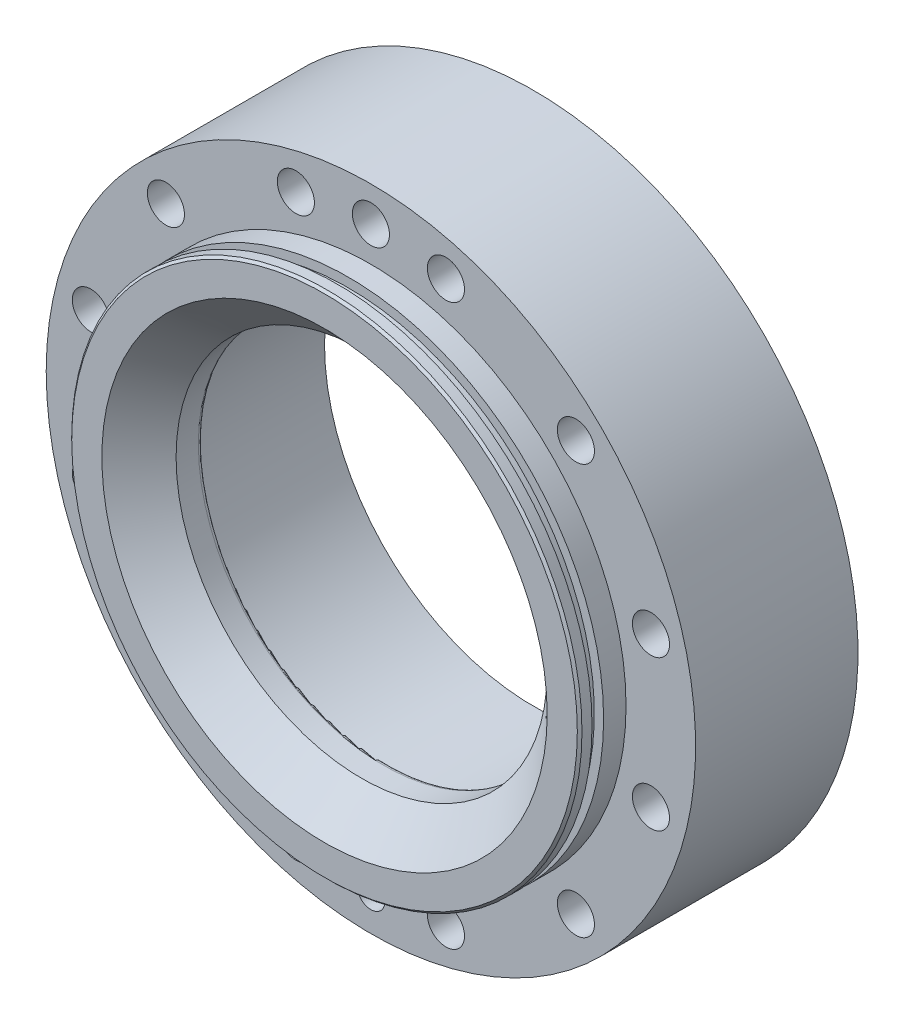
SolidWorks part; units mm, degrees
ref_plane "Front Plane" through (0, 0, 0) normal (0, 0, 1) x (1, 0, 0)
ref_plane "Top Plane" through (0, 0, 0) normal (0, 1, 0) x (1, 0, 0)
ref_plane "Right Plane" through (0, 0, 0) normal (1, 0, 0) x (0, 0, -1)
sketch "Sketch1" plane through (0, 0, 0) normal (0, 1, 0) x (1, 0, 0)
  line L0 (-55, -19.7958) -> (-55, -9.7958)
  line L2 (-55, -9.7958) -> (-70, -9.7958)
  line L3 (-55, -19.7958) -> (-40, -19.7958)
  line L4 (-40, -19.7958) -> (-40, -6)
  line L5 (-40, -6) -> (-45, -6)
  line L6 (-45, -6) -> (-45, 25.2042)
  line L7 (-45, 25.2042) -> (-70, 25.2042)
  line L8 (-70, 25.2042) -> (-70, -9.7958)
  line L12 (0, 52.7074) -> (0, -119.6493) construction
  point P2 (0, 0)
  point P3 (0, 0)
  dimension "D1" = 15
  dimension "D2" = 31.2042
revolve "Revolve1" add sketch "Sketch1" angle 360 about L12
sketch "Sketch2" plane through (0, 0, 9.7958) normal (0, 0, 1) x (1, 0, 0)
  line L0 (0, 62.5) -> (0, -62.5) construction
  circle A0 centre (0, 0) radius 62.5 construction
  circle A2 centre (0, -62.5) radius 3
  dimension "D1" = 125
  dimension "D3" = 6
extrude "Cut-Extrude1" cut sketch "Sketch2" against normal blind 9 contours A2
sketch "Sketch3" plane through (0, 0, 9.7958) normal (0, 0, 1) x (1, 0, 0)
  line L0 (0, 0) -> (0, 62.5) construction
  circle A0 centre (0, 62.5) radius 4
  dimension "D2" = 8
  dimension "D1" = 62.5
extrude "Cut-Extrude2" cut sketch "Sketch3" against normal blind 10
sketch "Bolt Holes" plane through (0, 0, 9.7958) normal (0, 0, 1) x (1, 0, 0)
  line L2 (-44.1942, 44.1942) -> (0, 0) construction
  line L3 (0, 0) -> (0, 62.5) construction
  circle A1 centre (0, 0) radius 62.5 construction
  point P0 (-60.3704, 16.1762)
  point P5 (-44.1942, 44.1942)
  point P8 (-16.1762, 60.3704)
  point P11 (16.1762, 60.3704)
  point P15 (44.1942, 44.1942)
  point P16 (60.3704, 16.1762)
  point P17 (60.3704, -16.1762)
  point P18 (44.1942, -44.1942)
  point P19 (16.1762, -60.3704)
  point P20 (-16.1762, -60.3704)
  point P21 (-44.1942, -44.1942)
  point P22 (-60.3704, -16.1762)
  point P23 (0, 0)
  point P30 (-44.1942, 44.1942)
  point P37 (44.1942, -44.1942)
  dimension "D3" = 45
  dimension "D2" = 125
  dimension "D1" = 12
sketch "Sketch9" plane through (0, 0, 0) normal (0, 1, 0) x (1, 0, 0)
  line L0 (-55, -9.7958) -> (-55, -19.7958) construction
  line L1 (-55, -17.1278) -> (-53, -17.1278)
  line L2 (-55, -17.1278) -> (-55, -14.6278)
  line L3 (-55, -14.6278) -> (-53, -14.6278)
  line L4 (-53, -17.1278) -> (-53, -14.6278)
  line L6 (0, 11.3077) -> (0, -18.9957) construction
  dimension "50" = 53
  dimension "D2" = 2.5
revolve "Oring groove" cut sketch "Sketch9" angle 360 about L6
chamfer "Chamfer1" distance 0.5 angle 45 1 edges at (-55, 0, 19.7958)
hole_wizard "Ø8.0mm Dowel Hole1" positions "Bolt Holes" profile "Sketch10" hole size "Ø8.0" standard "ANSI Metric" end condition through all
sketch "Sketch10" plane through (-60.3704, 16.1762, 9.7958) normal (1, 0, 0) x (0, -1, 0)
  line L0 (0, 0) -> (0, 35)
  line L1 (0, 35) -> (4, 35)
  line L2 (4, 35) -> (4, 0)
  line L5 (4, 0) -> (0, 0)
  line L11 (0, -6.35) -> (0, 107.95) construction
  dimension "Thru Hole Dia." = 8
  dimension "Thru Hole Depth" = 35
fillet "Fillet2" radius 1 1 edges at (-40, 0, 6)
chamfer "Chamfer2" distance 8 angle 45 1 edges at (-40, 0, 19.7958)
